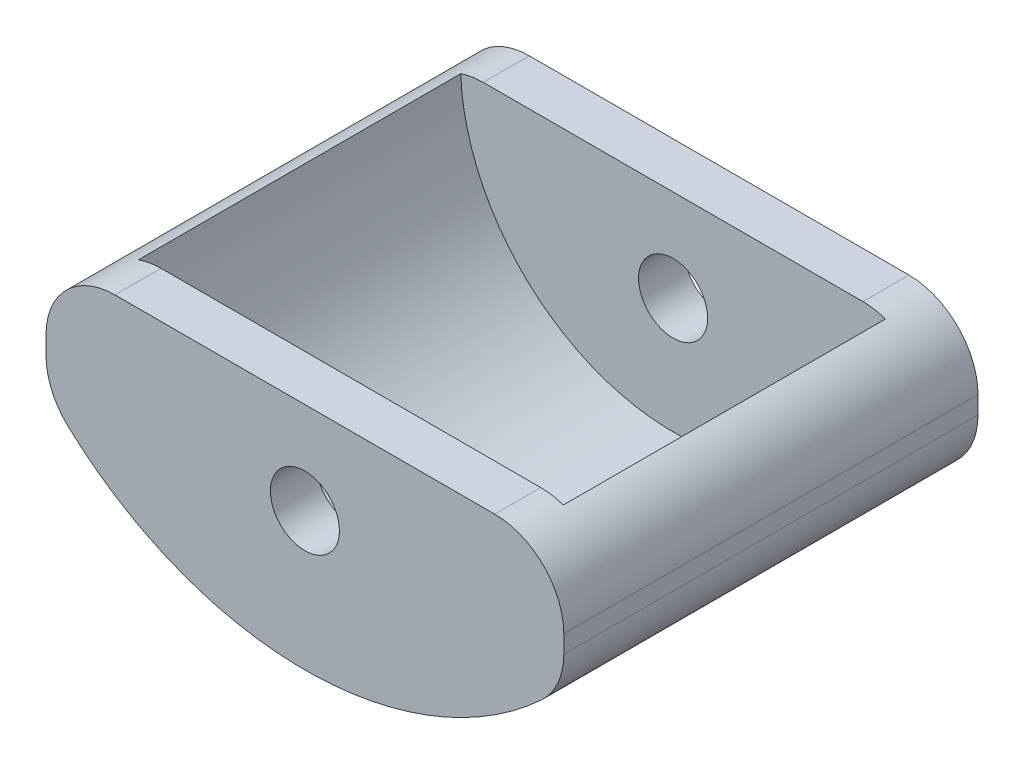
SolidWorks part; units mm, degrees
ref_plane "Front Plane" through (0, 0, 0) normal (0, 0, 1) x (1, 0, 0)
ref_plane "Top Plane" through (0, 0, 0) normal (0, 1, 0) x (1, 0, 0)
ref_plane "Right Plane" through (0, 0, 0) normal (1, 0, 0) x (0, 0, -1)
sketch "Sketch1" plane through (0, 0, 0) normal (0, 1, 0) x (1, 0, 0)
  line L1 (-11.25, 9) -> (11.25, 9)
  line L2 (-11.25, 9) -> (-11.25, -9)
  line L3 (-11.25, -9) -> (11.25, -9)
  line L4 (11.25, 9) -> (11.25, -9)
  dimension "D1" = 18
  dimension "D2" = 9
  dimension "D3" = 22.5
  dimension "D4" = 11.25
extrude "Boss-Extrude1" add sketch "Sketch1" along normal blind 10
sketch "Sketch2" plane through (0, 0, 9) normal (0, 0, 1) x (1, 0, 0)
  line L0 (-11.25, 10) -> (-11.25, 0) construction
  line L1 (11.25, 10) -> (11.25, 0) construction
  line L2 (-11.25, 5) -> (-11.25, 0)
  line L3 (-11.25, 0) -> (11.25, 0)
  line L4 (11.25, 0) -> (11.25, 5)
  line L5 (-11.25, 10) -> (11.25, 10) construction
  arc A0 (-11.25, 5) -> (11.25, 5) centre (0, 15.1866) ccw
  circle A1 centre (0, 6) radius 1.5
  point P17 (-11.25, 5)
  point P18 (11.25, 5)
  point P19 (0, 0.01)
  point P20 (-11.25, 5)
  point P21 (-11.25, 5)
  dimension "D1" = 3
  dimension "D2" = 11.25
  dimension "D3" = 4
  dimension "D4" = 5.99
extrude "Cut-Extrude1" cut sketch "Sketch2" against normal through all and the other way through all
ref_plane "Plane1" through (0, 0, 7) normal (0, 0, 1) x (1, 0, 0)
sketch "Sketch3" plane through (0, 0, 7) normal (0, 0, 1) x (1, 0, 0)
  line L5 (-7.5, 10) -> (7.5, 10)
  line L6 (11.25, 10) -> (-11.25, 10) construction
  line L7 (-5.7661, 10.0479) -> (5.7661, 10.0479)
  arc A3 (-7.5, 10) -> (7.5, 10) centre (0, 10.2071) ccw construction
  arc A4 (-9.2339, 9.9521) -> (9.2339, 9.9521) centre (0, 10.2071) ccw
  arc A5 (-5.7661, 10.0479) -> (5.7661, 10.0479) centre (0, 10.2071) ccw
  arc A6 (-5.7661, 10.0479) -> (-9.2339, 9.9521) centre (-7.5, 10) ccw
  arc A7 (9.2339, 9.9521) -> (5.7661, 10.0479) centre (7.5, 10) ccw
  arc A8 (-5.7661, 10.0479) -> (5.7661, 10.0479) centre (0, 10.2071) ccw
  point P5 (0, 2.7043)
  point P16 (0, 10)
  dimension "D3" = 5.7683
  dimension "D1" = 15
  dimension "D2" = 3.75
  dimension "D4" = 7.2957
extrude "Cut-Extrude2" cut sketch "Sketch3" against normal blind 14 contours A5 A7 A4 A6
sketch "Sketch4" plane through (0, 10, 0) normal (0, 1, 0) x (1, 0, 0)
  line L1 (-5.7645, 7) -> (5.7645, 7)
  line L2 (-5.7645, 7) -> (-5.7645, -7)
  line L3 (-5.7645, -7) -> (5.7645, -7)
  line L4 (5.7645, 7) -> (5.7645, -7)
extrude "Cut-Extrude3" cut sketch "Sketch4" against normal up to surface (7.011 mm away) up to face at (0, 5.4609, 0)
fillet "Fillet1" radius 3 4 edges at (11.25, 5, 0) (-11.25, 5, 0) (11.25, 10, 0) (-11.25, 10, 0)
